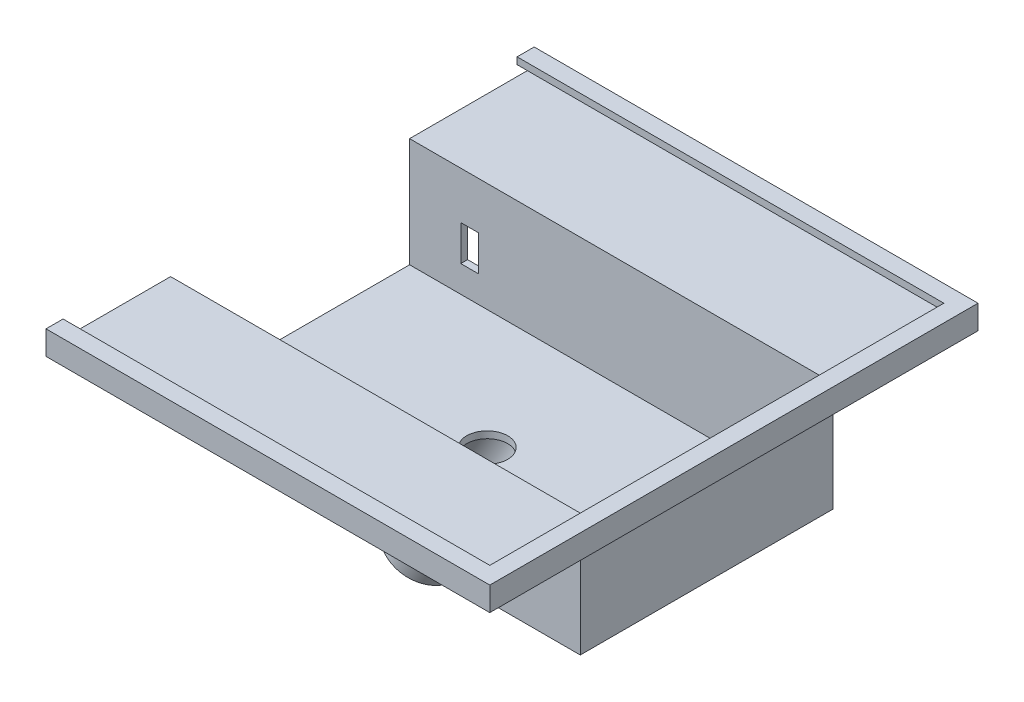
SolidWorks part; units mm, degrees
ref_plane "Plan de face" through (0, 0, 0) normal (0, 0, 1) x (1, 0, 0)
ref_plane "Plan de dessus" through (0, 0, 0) normal (0, 1, 0) x (1, 0, 0)
ref_plane "Plan de droite" through (0, 0, 0) normal (1, 0, 0) x (0, 0, -1)
sketch "Esquisse1" plane through (0, 0, 0) normal (0, 1, 0) x (1, 0, 0)
  line L0 (-120, 71.5) -> (-120, 35)
  line L1 (-120, 35) -> (0, 35)
  line L2 (0, 35) -> (0, -35)
  line L3 (0, -35) -> (-120, -35)
  line L4 (-120, -35) -> (-120, -71.5)
  line L5 (-120, -71.5) -> (10, -71.5)
  line L6 (10, -71.5) -> (10, 71.5)
  line L7 (10, 71.5) -> (-120, 71.5)
  point P2 (0, 0)
  dimension "D1" = 130
  dimension "D2" = 143
  dimension "D3" = 120
  dimension "D4" = 70
extrude "Boss.-Extru.1" add sketch "Esquisse1" along normal blind 2
sketch "Esquisse2" plane through (0, 2, 0) normal (0, 1, 0) x (1, 0, 0)
  line L0 (-120, 71.5) -> (10, 71.5)
  line L1 (10, 71.5) -> (10, -71.5)
  line L2 (10, -71.5) -> (-120, -71.5)
  line L3 (-120, -71.5) -> (-120, -69.5)
  line L4 (-120, -35) -> (-120, -71.5) construction
  line L5 (-120, -69.5) -> (8, -69.5)
  line L6 (8, -69.5) -> (8, 69.5)
  line L7 (8, 69.5) -> (-120, 69.5)
  line L8 (-120, 71.5) -> (-120, 35) construction
  line L9 (-120, 69.5) -> (-120, 71.5)
  dimension "D1" = 2
  dimension "D2" = 2
  dimension "D3" = 2
extrude "Boss.-Extru.2" add sketch "Esquisse2" along normal blind 3
sketch "Esquisse3" plane through (0, 5, 0) normal (0, 1, 0) x (1, 0, 0)
  line L1 (-120, 69.5) -> (-120, 35) construction
  line L2 (-120, 66.5) -> (5, 66.5)
  line L3 (5, 66.5) -> (5, -66.5)
  line L4 (5, -66.5) -> (-120, -66.5)
  line L5 (-120, -35) -> (-120, -69.5) construction
  line L6 (-120, -66.5) -> (-120, -71.5)
  line L7 (-120, -71.5) -> (10, -71.5)
  line L8 (10, -71.5) -> (10, 71.5)
  line L9 (10, 71.5) -> (-120, 71.5)
  line L10 (-120, 66.5) -> (-120, 71.5)
  dimension "D1" = 5
  dimension "D2" = 5
  dimension "D3" = 5
extrude "Boss.-Extru.3" add sketch "Esquisse3" along normal blind 2
sketch "Esquisse4" plane through (0, 0, 0) normal (0, -1, 0) x (1, 0, 0)
  line L0 (-120, 35) -> (0, 35)
  line L1 (0, 35) -> (0, -35)
  line L2 (0, -35) -> (-120, -35)
  line L3 (-120, -35) -> (-120, -37)
  line L4 (-120, -71.5) -> (-120, -35) construction
  line L5 (-120, -37) -> (2, -37)
  line L6 (2, -37) -> (2, 37)
  line L7 (2, 37) -> (-120, 37)
  line L8 (-120, 35) -> (-120, 71.5) construction
  line L9 (-120, 37) -> (-120, 35)
  dimension "D1" = 2
  dimension "D2" = 2
  dimension "D3" = 2
extrude "Boss.-Extru.4" add sketch "Esquisse4" along normal blind 30
sketch "Esquisse5" plane through (0, -30, 0) normal (0, -1, 0) x (1, 0, 0)
  line L1 (-120, 37) -> (2, 37)
  line L2 (-120, 37) -> (-120, -37)
  line L3 (-120, -37) -> (2, -37)
  line L4 (2, 37) -> (2, -37)
extrude "Boss.-Extru.5" add sketch "Esquisse5" along normal blind 2
sketch "Esquisse8" plane through (0, 0, 0) normal (0, 0, 1) x (1, 0, 0)
  line L0 (0, 0) -> (-47.4032, -82.1048) construction
  line L1 (0, 0) -> (-127.1616, 0) construction
  dimension "D1" = 60
sketch3d "Esquisse3D1"
  line L0 (0, 0, 0) -> (-47.4032, -82.1048, 0) construction
sketch "Esquisse9" plane through (-47.4032, -82.1048, 0) normal (0.5, 0.866, 0) x (0.866, -0.5, 0)
  line L0 (-87.923, -37) -> (-87.923, 37) construction
  circle A0 centre (-37.923, 0) radius 8.25
  circle A1 centre (-37.923, 0) radius 10.25
  dimension "D1" = 16.5
  dimension "D2" = 2
  dimension "D3" = 50
extrude "Boss.-Extru.7" add sketch "Esquisse9" along normal up to next
sketch "Esquisse10" plane through (0, -32, 0) normal (0, -1, 0) x (1, 0, 0)
  line L0 (0, 0) -> (-127.1616, 0) construction
  circle A0 centre (-62.265, 0) radius 6
  ellipse E0 centre (-62.265, 0) end of major axis (-74.1007, 0) minor radius 10.25 construction
  dimension "D1" = 12
extrude "Enlèv. mat.-Extru.2" cut sketch "Esquisse10" against normal up to next
sketch "Esquisse12" plane through (0, 0, -37) normal (0, 0, -1) x (-1, 0, 0)
  line L0 (120, -32) -> (120, 0) construction
  line L1 (105, -11.8) -> (99.8, -11.8)
  line L2 (105, -11.8) -> (105, -22.2)
  line L3 (105, -22.2) -> (99.8, -22.2)
  line L4 (99.8, -11.8) -> (99.8, -22.2)
  line L6 (120, -32) -> (-2, -32) construction
  dimension "D1" = 10.4
  dimension "D2" = 5.2
  dimension "D3" = 15
  dimension "D4" = 9.8
extrude "Enlèv. mat.-Extru.4" cut sketch "Esquisse12" against normal through all
fillet "Congé1" radius 5 1 edges at (-74.1007, -32, 0)
